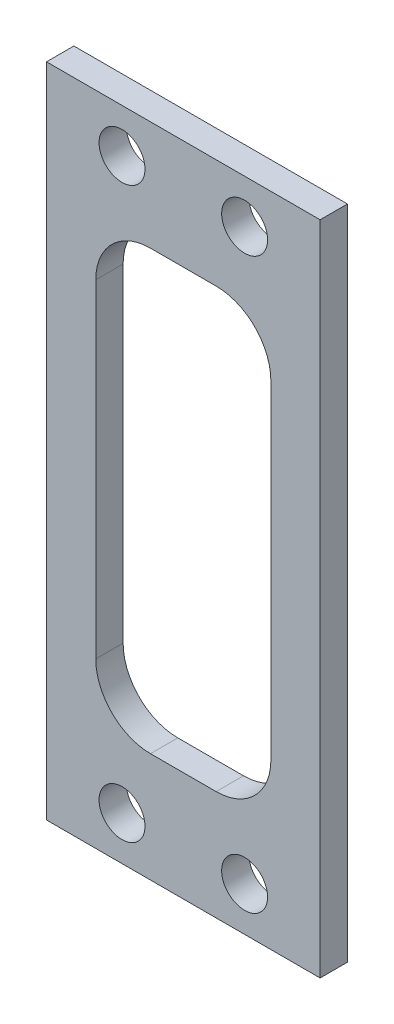
SolidWorks part; units mm, degrees
ref_plane "Front" through (0, 0, 0) normal (0, 0, 1) x (1, 0, 0)
ref_plane "Top" through (0, 0, 0) normal (0, 1, 0) x (1, 0, 0)
ref_plane "Right" through (0, 0, 0) normal (1, 0, 0) x (0, 0, -1)
sketch "Sketch1" plane through (0, 0, 0) normal (0, 0, 1) x (1, 0, 0)
  line L1 (-15.875, -38.1) -> (15.875, -38.1)
  line L2 (-15.875, -38.1) -> (-15.875, 38.1)
  line L3 (-15.875, 38.1) -> (15.875, 38.1)
  line L4 (15.875, -38.1) -> (15.875, 38.1)
  line L5 (-15.875, -38.1) -> (15.875, 38.1) construction
  line L6 (-15.875, 38.1) -> (15.875, -38.1) construction
  line L7 (-10.16, 25.4) -> (10.16, 25.4)
  line L8 (-10.16, 25.4) -> (-10.16, -25.4)
  line L9 (-10.16, -25.4) -> (10.16, -25.4)
  line L10 (10.16, 25.4) -> (10.16, -25.4)
  line L11 (-10.16, 25.4) -> (10.16, -25.4) construction
  line L12 (-10.16, -25.4) -> (10.16, 25.4) construction
  point P0 (0, 0)
  point P6 (0, 0)
  dimension "D1" = 31.75
  dimension "D2" = 76.2
  dimension "D3" = 20.32
  dimension "D4" = 50.8
extrude "Boss-Extrude1" add sketch "Sketch1" along normal blind 3.175
fillet "Fillet1" radius 6.35 4 edges at (-10.16, 25.4, 1.5875) (10.16, 25.4, 1.5875) (-10.16, -25.4, 1.5875) (10.16, -25.4, 1.5875)
sketch "Sketch2" plane through (0, 0, 3.175) normal (0, 0, 1) x (1, 0, 0)
  line L0 (-3.81, -25.4) -> (3.81, -25.4) construction
  line L1 (0, -38.1) -> (0, -25.4) construction
  line L2 (-15.875, -38.1) -> (15.875, -38.1) construction
  circle A0 centre (7.112, -33.02) radius 2.665
  dimension "D1" = 5.33
  dimension "D2" = 7.62
  dimension "D3" = 7.112
extrude "Cut-Extrude1" cut sketch "Sketch2" against normal up to next
mirror "Mirror1" about plane through (0, 0, 0) normal (1, 0, 0) of "Cut-Extrude1"
mirror "Mirror2" about plane through (0, 0, 0) normal (0, 1, 0) of "Mirror1"
